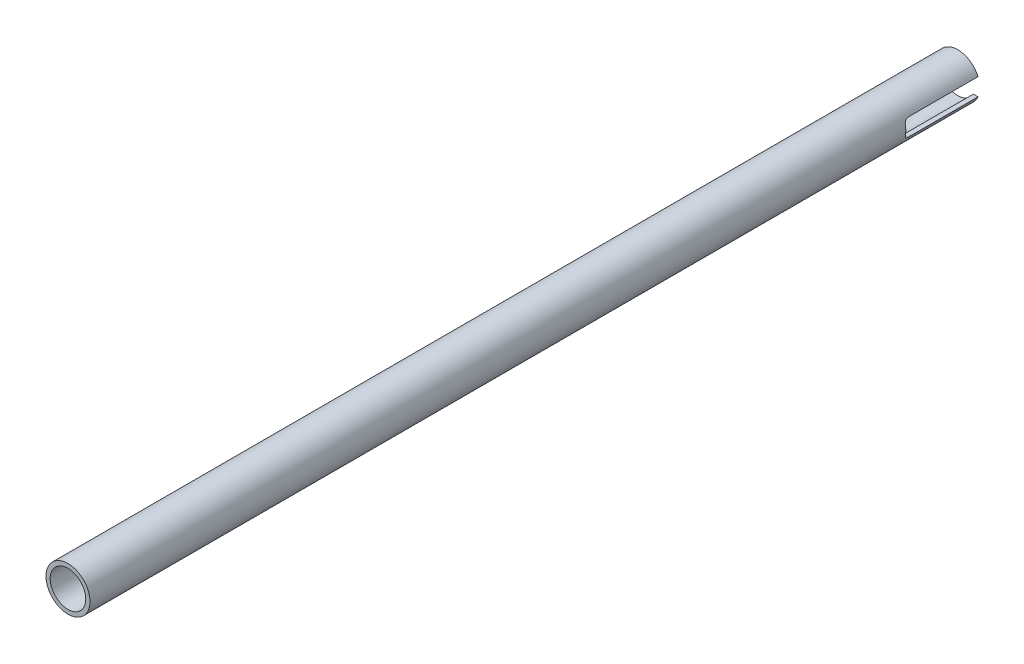
SolidWorks part; units mm, degrees
material "AISI 4130 Steel, annealed at 865C"
ref_plane "Front Plane" through (0, 0, 0) normal (0, 0, 1) x (1, 0, 0)
ref_plane "Top Plane" through (0, 0, 0) normal (0, 1, 0) x (1, 0, 0)
ref_plane "Right Plane" through (0, 0, 0) normal (1, 0, 0) x (0, 0, -1)
sketch "Sketch1" plane through (0, 0, 0) normal (0, 0, 1) x (1, 0, 0)
  circle A0 centre (0, 0) radius 6.477
  circle A1 centre (0, 0) radius 8.001
  dimension "D1" = 12.954
  dimension "D2" = 16.002
extrude "Boss-Extrude1" add sketch "Sketch1" along normal blind 323.85
sketch "Sketch2" plane through (0, 0, 0) normal (1, 0, 0) x (0, 0, -1)
  line L0 (0, 3.175) -> (-25.4, 3.175)
  line L1 (0, 55) -> (0, -55) construction
  line L2 (-25.4, -3.175) -> (0, -3.175)
  line L3 (-26.924, 1.651) -> (-26.924, -1.651)
  line L4 (0, -8.001) -> (0, 8.001) construction
  arc A0 (-26.924, 1.651) -> (-25.4, 3.175) centre (-25.4, 1.651) cw
  arc A1 (-25.4, -3.175) -> (-26.924, -1.651) centre (-25.4, -1.651) cw
  dimension "D5" = 25.4
  dimension "D6" = 26.924
  dimension "D1" = 26.924
  dimension "D2" = 25.4
  dimension "D3" = 6.35
  dimension "D4" = 3.175
extrude "Cut-Extrude2" cut sketch "Sketch2" against normal through all both and the other way through all
